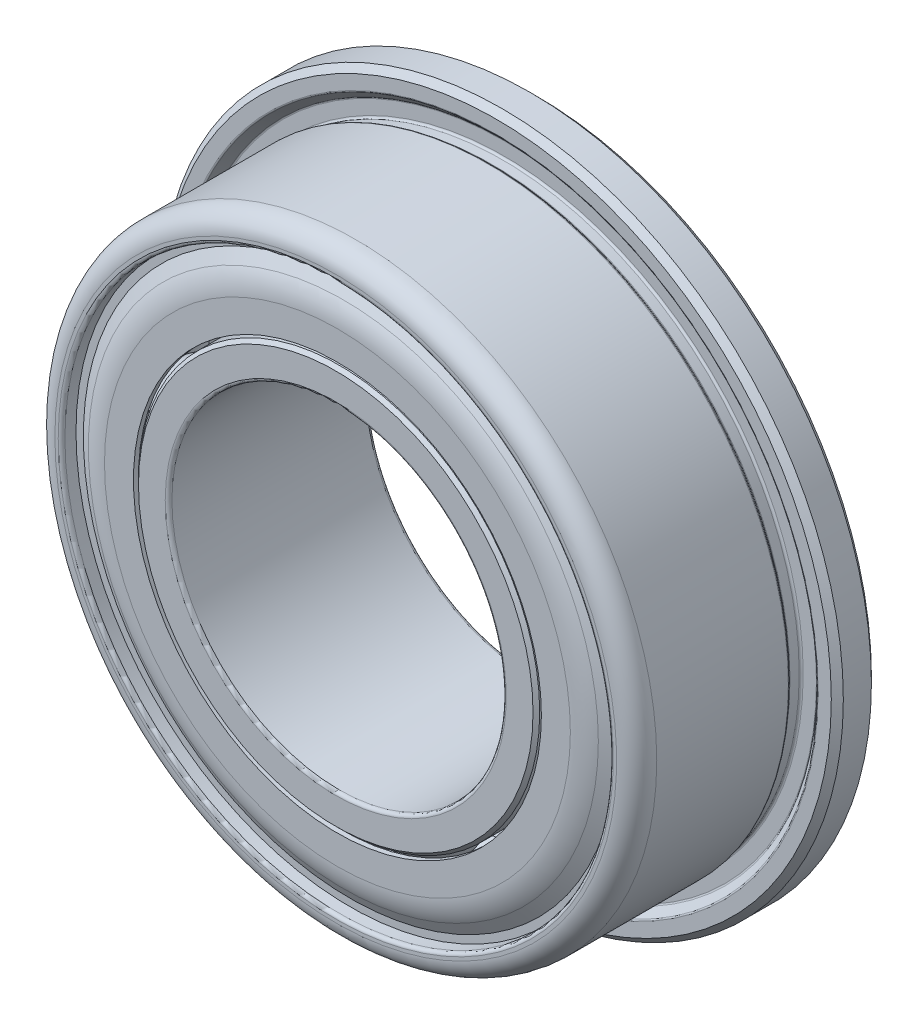
SolidWorks part; units mm, degrees
note: '?' marks a value the reader was unsure of.
ref_plane "Front Plane" through (0, 0, 0) normal (0, 0, 1) x (1, 0, 0)
ref_plane "Top Plane" through (0, 0, 0) normal (0, 1, 0) x (1, 0, 0)
ref_plane "Right Plane" through (0, 0, 0) normal (1, 0, 0) x (0, 0, -1)
sketch "Sketch1" plane through (0, 0, 0) normal (1, 0, 0) x (0, 0, -1)
  line L0 (-1.5, 0) -> (1.5, 0) construction
  line L1 (0, 4.5) -> (0, -4.5) construction
  line L2 (1.5, 4.5) -> (-1.5, 4.5)
  line L4 (-1.5, 4.5) -> (-1.5, 4.1)
  line L5 (-1.5, 4.1) -> (-0.6606, 4.1)
  line L6 (1.5, 4.1) -> (0.6606, 4.1)
  line L7 (1.5, 4.5) -> (1.5, 4.1)
  line L9 (0, 4.5) -> (0, 3.5) construction
  line L10 (0, 3.5) -> (0, 2.5) construction
  line L11 (-1.5, -4.1) -> (-1.5, 4.1) construction
  line L12 (0.9, -5.1) -> (1.5, -5.1)
  line L13 (0.9, -5.1) -> (0.9, 5.1)
  line L14 (0.9, 5.1) -> (1.5, 5.1)
  line L15 (1.5, -5.1) -> (1.5, 5.1)
  line L16 (0.9, -5.1) -> (1.5, 5.1) construction
  line L17 (0.9, 5.1) -> (1.5, -5.1) construction
  line L18 (-1.5, -3) -> (-1.5, 3)
  line L24 (0, -4.5) -> (-1.5, -4.5)
  line L25 (0, 2.5) -> (0, 4.5) construction
  line L26 (-1.5, 3) -> (-1.5, 2.5)
  line L27 (-1.5, 2.5) -> (1.5, 2.5)
  line L28 (1.5, 2.5) -> (1.5, 3)
  line L29 (1.5, 3) -> (0.4606, 3)
  line L30 (-1.5, 3) -> (-0.4606, 3)
  line L31 (-0.6606, 4.1) -> (-0.6606, 3.88)
  line L32 (-0.6606, 3.88) -> (-0.4606, 3.88)
  line L33 (0.6606, 4.1) -> (0.6606, 3.88)
  line L34 (0.6606, 3.88) -> (0.4606, 3.88)
  arc A3 (-0.4606, 3) -> (0.4606, 3) centre (0, 3.5) ccw
  circle A5 centre (0, 3.4502) radius 0.6
  arc A6 (-0.4606, 3.88) -> (0.4606, 3.88) centre (0, 3.4502) cw
  point P7 (-1.5, 4.1)
  point P13 (-1.4, 4.1)
  point P14 (0, 2.5)
  point P15 (1.2, 0)
  point P22 (1.5, 0)
  point P25 (-1.5, 0)
  point P27 (-1.5, 0)
  point P28 (-1.3, 4.1)
  point P29 (-1.2, 4.1)
  point P30 (-1.1, 4.1)
  point P31 (-1, 4.1)
  point P32 (-0.9, 4.1)
  point P33 (-0.8, 4.1)
  point P46 (0, 4.0802)
  point P50 (0, 2.8202)
  point P51 (0, 2.8502)
  point P52 (0, 4.0502)
  dimension "D3" = 1.2
  dimension "Shaft Dia" = 5
  dimension "Flange Thickness" = 0.6
  dimension "Flange OD" = 10.2
  dimension "D11" = 8.2
  dimension "D10" = 6
  dimension "Width" = 3
  dimension "OD" = 9
  dimension "D4" = 0.03
  dimension "D2" = 0.03
  dimension "D5" = 0.2
  dimension "D6" = 0.1
  dimension "D7" = 0.88
  dimension "D1" = 8
sketch "Sketch2" plane through (0, 0, 0) normal (0, 0, 1) x (1, 0, 0)
  line L0 (0, -3) -> (0, 3) construction
  circle A0 centre (0, 0) radius 2.5
  dimension "D1" = 5
sketch "Sketch3" plane through (0, 0, 0) normal (1, 0, 0) x (0, 0, -1)
  line L2 (-1.5, 4.5) -> (-1.5, 4.1) construction
  line L3 (1.5, 4.5) -> (-1.5, 4.5) construction
  line L4 (1.5, 4.5) -> (1.5, 4.1) construction
  line L5 (1.5, 4.1) -> (0.6606, 4.1) construction
  line L6 (-1.5, 4.1) -> (-0.6606, 4.1) construction
  line L13 (-1.5, 4.5) -> (-1.5, 4.1)
  line L21 (1.5, 4.5) -> (-1.5, 4.5)
  line L22 (1.5, 4.5) -> (1.5, 4.1)
  line L23 (1.5, 4.1) -> (0.6606, 4.1)
  line L24 (-1.5, 4.1) -> (-0.6606, 4.1)
  line L25 (1.5, 2.5) -> (-1.5, 2.5)
  line L27 (-1.5, 2.5) -> (-1.5, 3)
  line L28 (-1.5, 3) -> (-0.4606, 3)
  line L29 (0.6606, 4.1) -> (0.6606, 3.88) construction
  line L30 (1.5, 2.5) -> (1.5, 3)
  line L31 (1.5, -5.1) -> (1.5, 5.1) construction
  line L32 (1.5, 3) -> (0.4606, 3)
  line L33 (0.6606, 3.88) -> (0.4606, 3.88) construction
  line L34 (-0.6606, 3.88) -> (-0.4606, 3.88) construction
  line L35 (-0.6606, 4.1) -> (-0.6606, 3.88) construction
  line L36 (0.6606, 4.1) -> (0.6606, 3.88)
  line L37 (0.6606, 3.88) -> (0.4606, 3.88)
  line L38 (-0.6606, 3.88) -> (-0.4606, 3.88)
  line L39 (-0.6606, 4.1) -> (-0.6606, 3.88)
  arc A4 (0.4606, 3.88) -> (-0.4606, 3.88) centre (0, 3.4502) ccw construction
  arc A5 (-0.4606, 3) -> (0.4606, 3) centre (0, 3.5) ccw construction
  arc A6 (-0.4606, 3) -> (0.4606, 3) centre (0, 3.5) ccw
  arc A7 (0.4606, 3.88) -> (-0.4606, 3.88) centre (0, 3.4502) ccw
  point P15 (0, 2.5)
revolve "Revolve1" add sketch "Sketch3" angle 360 about L0
sketch "Sketch5" plane through (0, 0, 0) normal (1, 0, 0) x (0, 0, -1)
  line L0 (-0.6, 3.4502) -> (0.6, 3.4502)
  line L1 (0, 4.5) -> (0, -4.5) construction
  circle A0 centre (0, 3.4502) radius 0.6 construction
  arc A1 (-0.6, 3.4502) -> (0.6, 3.4502) centre (0, 3.4502) cw
revolve "Revolve3" add sketch "Sketch5" angle 360 about L0
ref_axis "Axis1" through (0, 0, -1.5) along (0, 0, 1)?
pattern_circular "CirPattern1" count 8 over 360 about axis through (0, 0, 0) along (0, 0, 1) of bodies 122
sketch "Sketch6" plane through (0, 0, 0) normal (1, 0, 0) x (0, 0, -1)
  line L1 (-1.475, 3) -> (-1.475, 3.4832)
  line L2 (-1.3866, 3.8132) -> (-1.2845, 3.99)
  line L4 (-1.2845, 3.99) -> (-1.1979, 3.99) construction
  line L5 (-1.2845, 3.99) -> (-1.2845, 4.1)
  line L6 (-1.2845, 4.1) -> (-1.1979, 4.1)
  line L7 (-1.1979, 3.99) -> (-1.4, 3.6399)
  line L8 (-1.4, 3.6399) -> (-1.4, 3)
  line L9 (-1.4, 3) -> (-1.475, 3)
  line L10 (0, 4.5) -> (0, -4.5) construction
  line L11 (-1.1979, 4.1) -> (-1.1979, 3.99)
  line L12 (-1.5, 4.1) -> (-0.6606, 4.1) construction
  line L14 (0, 4.5) -> (0, 4.0802) construction
  arc A0 (-1.475, 3.4832) -> (-1.3866, 3.8132) centre (-0.815, 3.4832) cw
  point P22 (-1.475, 3.66)
  dimension "D8" = 0.66
  dimension "D1" = 30
  dimension "D3" = 0.075
  dimension "D2" = 0.025
  dimension "D4" = 0.075
  dimension "D6" = 0.33
  dimension "D5" = 1.1
  dimension "D7" = 0.11
revolve "Revolve4" add sketch "Sketch6" angle 360 about L0
mirror "Mirror1" about plane through (0, 0, 0) normal (0, 0, 1) of bodies 138
sketch "Sketch9" plane through (0, 0, 1.475) normal (0, 0, 1) x (1, 0, 0)
  circle A2 centre (0, 0) radius 3.05
  circle A3 centre (0, 0) radius 3.05
  dimension "D1" = 0.05
extrude "Cut-Extrude1" cut sketch "Sketch9" against normal through all
sketch "Sketch7" plane through (0, 0, 0) normal (1, 0, 0) x (0, 0, -1)
  line L0 (1.5, 0) -> (-1.5, 0) construction
  line L2 (0.9, 5.1) -> (1.5, 5.1)
  line L3 (0.9, 5.1) -> (0.9, 4.1)
  line L4 (0.9, 4.1) -> (1.5, 4.1)
  line L5 (1.5, 5.1) -> (1.5, 4.1)
revolve "Revolve5" add sketch "Sketch7" angle 360 about L0
fillet "Fillet2" radius 0.3 1 edges at (4.5, 0, 1.5)
fillet "Fillet3" radius 0.05 4 edges at (4.1, 0, -1.5) (4.1, 0, 1.5) (4.1, 0, -0.6606) (4.1, 0, 0.6606)
fillet "Fillet6" radius 0.05 4 edges at (3, 0, -1.5) (3, 0, -0.4606) (3, 0, 0.4606) (3, 0, 1.5)
sketch "Sketch8" plane through (0, 0, 0) normal (1, 0, 0) x (0, 0, -1)
  line L7 (0.9, 5.1) -> (0.9, 4.5) construction
  line L8 (0.9, 4.8) -> (1.02, 4.68)
  line L9 (1.02, 4.68) -> (1.02, 4.44)
  line L10 (1.02, 4.44) -> (0.84, 4.44)
  line L11 (0.84, 4.44) -> (0.78, 4.5)
  line L12 (0.9, 4.5) -> (-1.2, 4.5) construction
  line L13 (0.78, 4.5) -> (0.9, 4.5)
  line L14 (0.9, 4.5) -> (0.9, 4.8)
  dimension "D1" = 45
  dimension "D2" = 45
  dimension "D3" = 0.12
  dimension "D4" = 0.06
  dimension "D5" = 0.06
revolve "Cut-Revolve1" cut sketch "Sketch8" angle 360 about L0
fillet "Fillet5" radius 0.03 5 edges at (4.5, 0, -0.78) (4.44, 0, -0.84) (4.44, 0, -1.02) (4.68, 0, -1.02) (4.8, 0, -0.9)
chamfer "Chamfer1" distance 0.09 angle 45 2 edges at (-5.1, 0, -0.9) (-5.1, 0, -1.5)
fillet "Fillet7" radius 0.05 2 edges at (2.5, 0, 1.5) (2.5, 0, -1.5)
equation "\"Balls@CirPattern1\"=\"D1@Sketch1\""
equation "\"D3@Sketch8\" = \"Flange Thickness@Sketch1\" * .2"
equation "\"D4@Sketch8\" = \"D3@Sketch8\" * .5"
equation "\"D5@Sketch8\" = \"D3@Sketch8\" * .5"
equation "\"D1@Chamfer1\"=\"Flange Thickness@Sketch1\"*.15"
equation "\"D1@Fillet6\"=\"D1@Fillet3\""
equation "\"D4@Sketch1\"=\"D2@Sketch1\""
equation "\"D7@Sketch1\" =  ( \"D11@Sketch1\" - \"D10@Sketch1\" )  * .40"
equation "\"D3@Sketch6\"=\"D4@Sketch6\""
equation "\"D8@Sketch6\"=\"D6@Sketch6\"*2"
